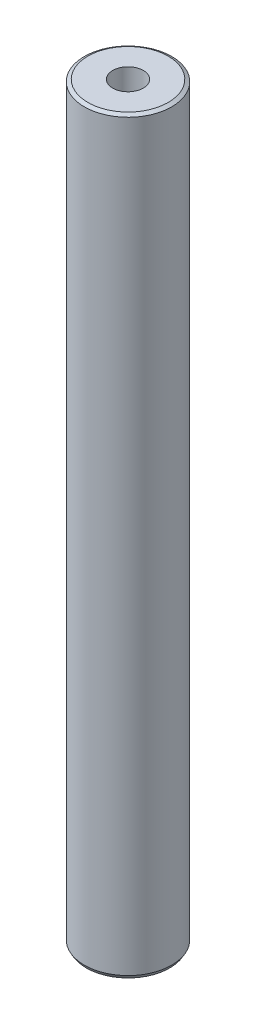
SolidWorks part; units mm, degrees
ref_plane "Front Plane" through (0, 0, 0) normal (0, 0, 1) x (1, 0, 0)
ref_plane "Top Plane" through (0, 0, 0) normal (0, 1, 0) x (1, 0, 0)
ref_plane "Right Plane" through (0, 0, 0) normal (1, 0, 0) x (0, 0, -1)
sketch "Sketch1" plane through (0, 0, 0) normal (0, 1, 0) x (1, 0, 0)
  circle A0 centre (0, 0) radius 35
  dimension "SHAFT_OD" = 70
extrude "Boss-Extrude1" add sketch "Sketch1" along normal blind 600
sketch "Sketch2" plane through (0, 0, 0) normal (0, 1, 0) x (1, 0, 0)
  circle A0 centre (0, 0) radius 12.2738
  dimension "BORE_D" = 24.5475
extrude "Cut-Extrude1" cut sketch "Sketch2" along normal through all
chamfer "Chamfer1" distance 1.628 angle 60 2 edges at (0, 600, 35) (0, 0, 35) first distance on face at (0, 600, 35) first distance on face at (0, 0, 12.2738)
